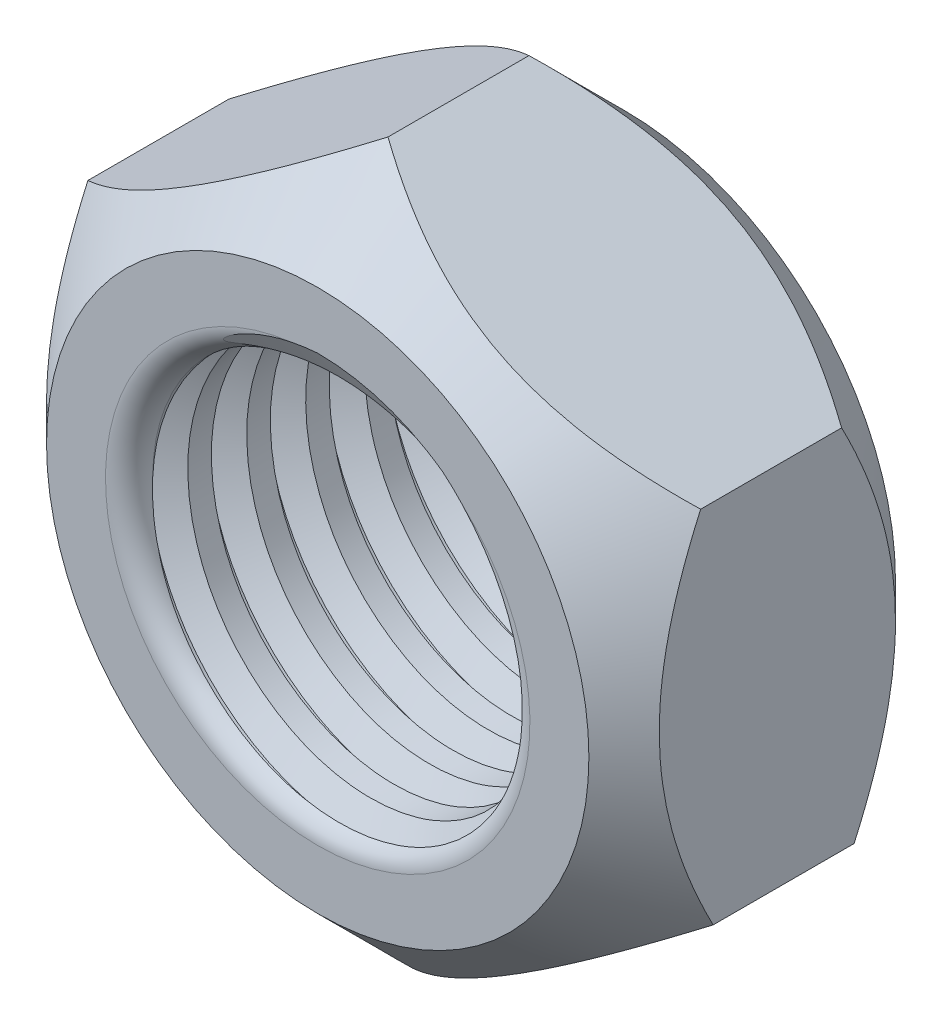
SolidWorks part; units mm, degrees
ref_plane "Front Plane" through (0, 0, 0) normal (0, 0, 1) x (1, 0, 0)
ref_plane "Top Plane" through (0, 0, 0) normal (0, 1, 0) x (1, 0, 0)
ref_plane "Right Plane" through (0, 0, 0) normal (1, 0, 0) x (0, 0, -1)
sketch "Sketch1" plane through (0, 0, 0) normal (0, 0, 1) x (1, 0, 0)
  line L1 (6.6285, -3.5208) -> (6.3634, 3.9801)
  line L2 (6.3634, 3.9801) -> (-0.2652, 7.5009)
  line L3 (-0.2652, 7.5009) -> (-6.6285, 3.5208)
  line L4 (-6.6285, 3.5208) -> (-6.3634, -3.9801)
  line L5 (-6.3634, -3.9801) -> (0.2652, -7.5009)
  line L6 (0.2652, -7.5009) -> (6.6285, -3.5208)
  circle A0 centre (0, 0) radius 6.5 construction
  dimension "D1" = 13
extrude "Boss-Extrude1" add sketch "Sketch1" along normal mid plane 6.5 contours L3 L4 L5 L6 L1 L2
sketch "Sketch5" plane through (0, 0, 3.25) normal (0, 0, 1) x (1, 0, 0)
  circle A0 centre (0, 0) radius 4
  dimension "D1" = 8
extrude "Cut-Extrude2" cut sketch "Sketch5" against normal blind 9
sketch "Sketch6" plane through (0, 0, 3.25) normal (0, 0, 1) x (1, 0, 0)
  circle A0 centre (0, 0) radius 5.75
extrude "Cut-Extrude3" cut sketch "Sketch6" against normal mid plane 4 draft 45 flip side to cut
mirror "Mirror1" about plane through (0, 0, 0) normal (0, 0, 1) of "Cut-Extrude3"
fillet "Fillet1" radius 0.5 2 edges at (4, 0, -3.25) (4, 0, 3.25)
thread "Thread3" pitch 1 method cut profile "Thread Profile4" start angle 0, offset 2, length 0, pitch 1.25, diameter 8
ref_plane "Plane4" through (-4, 0, 5.25) normal (0, -1, 0) x (-1, 0, 0)
sketch "Thread Profile4" plane through (-4, 0, 5.25) normal (0, -1, 0) x (-1, 0, 0)
  line L0 (0, 0) -> (0, 1) construction
  line L1 (0, 0) -> (0.5413, 0.3125)
  line L2 (0.5413, 0.3125) -> (0.5413, 0.4375)
  line L3 (0.5413, 0.4375) -> (0, 0.75)
  line L4 (0.5413, 0.375) -> (0, 0.375) construction
  line L11 (0, 0) -> (0, 0.75)
  point P2 (0, 0)
  dimension "Pitch" = 1
  dimension "Profile_Angle" = 60
  dimension "Profile_Land" = 0.125
  dimension "Profile_Height" = 0.5413
